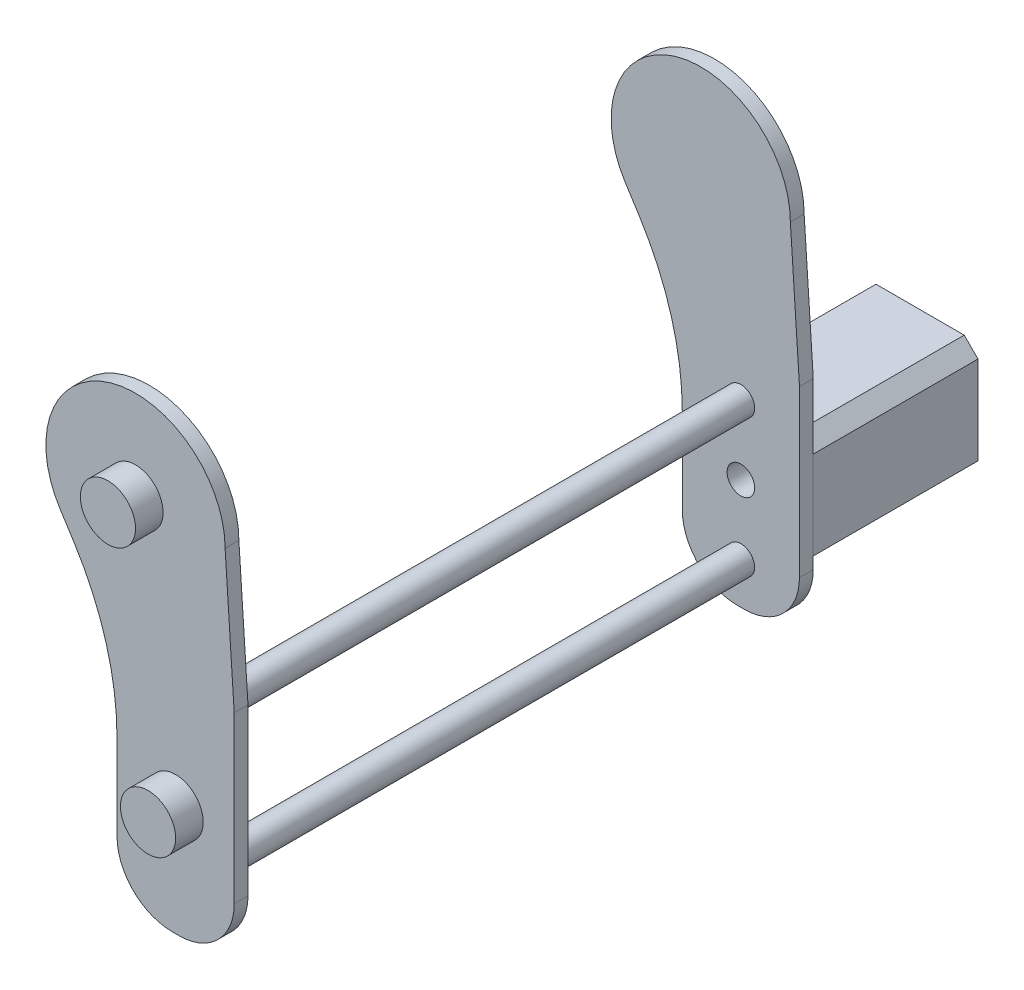
SolidWorks part; units mm, degrees
note: The reader was unsure of these and kept them because the rebuilt part matched: shared geometry of "Sketch5<3>", "Sketch5<4>".
ref_plane "Front Plane" through (0, 0, 0) normal (0, 0, 1) x (1, 0, 0)
ref_plane "Top Plane" through (0, 0, 0) normal (0, 1, 0) x (1, 0, 0)
ref_plane "Right Plane" through (0, 0, 0) normal (1, 0, 0) x (0, 0, -1)
sketch "Sketch5" plane through (0, 0, 0) normal (0, 0, 1) x (1, 0, 0)
  line L0 (14.55, -65) -> (14.55, -115) construction
  line L5 (0, 0) -> (0, -283.4803) construction
  line L7 (35.8, -50) -> (32.5, 0)
  line L11 (35.8, -68.75) -> (-6.7, -68.75)
  line L12 (35.8, -68.75) -> (35.8, -111.25)
  line L13 (35.8, -111.25) -> (-6.7, -111.25)
  line L14 (-6.7, -68.75) -> (-6.7, -111.25)
  line L15 (35.8, -68.75) -> (-6.7, -111.25) construction
  line L16 (35.8, -111.25) -> (-6.7, -68.75) construction
  line L17 (-6.7, -130) -> (35.8, -130)
  line L18 (-6.7, -130) -> (-6.7, -79.1253)
  line L19 (-6.7, -50) -> (35.8, -50) construction
  line L20 (35.8, -130) -> (35.8, -50)
  line L21 (-6.7, -130) -> (35.8, -50) construction
  line L22 (-6.7, -50) -> (35.8, -130) construction
  line L23 (-22.339, -25.4296) -> (-27.4173, -17.4511)
  line L25 (35.55, -111) -> (-6.45, -111)
  line L26 (35.55, -111) -> (35.55, -69)
  line L27 (35.55, -69) -> (-6.45, -69)
  line L28 (-6.45, -111) -> (-6.45, -69)
  line L29 (35.55, -111) -> (-6.45, -69) construction
  line L30 (35.55, -69) -> (-6.45, -111) construction
  circle A0 centre (14.55, -65) radius 5
  circle A1 centre (14.55, -115) radius 5
  circle A2 centre (0, 0) radius 32.5
  arc A3 (-6.7, -79.1253) -> (-22.339, -25.4296) centre (-106.7, -79.1253) ccw
  point P0 (14.55, -90)
  point P17 (14.55, -90)
  point P18 (14.55, -90)
  dimension "D3" = 10
  dimension "D7" = 65
  dimension "D8" = 100
  dimension "D1" = 42.5
  dimension "D2" = 50
  dimension "D4" = 14.55
  dimension "D5" = 90
  dimension "D6" = 15
  dimension "D9" = 42
extrude "Boss-Extrude4" add sketch "Sketch5" along normal blind 5 contours A2 | A3 L18 L11 L20 L7 A2 L23 A0 | L11 L14 L13 L12 | L17 L20 L13 L18 A1 | A0 | A1 | A1 L25 L28 L27 A0 L11 L14 L13 | A1 L25 L26 L27 A0 L28
extrude "Boss-Extrude5" add sketch "Sketch5<3>" along normal blind 105 contours A0 | A1
sketch "Sketch5<3>" plane through (0, 0, 0) normal (0, 0, 1) x (1, 0, 0) same geometry as "Sketch5"
fillet "Fillet3" radius 20 2 edges at (-6.7, -130, 2.5) (35.8, -130, 2.5)
sketch "Sketch9" plane through (0, 0, 0) normal (0, 0, -1) x (-1, 0, 0)
  circle A0 centre (0, 0) radius 10
  dimension "D1" = 20
extrude "Boss-Extrude8" add sketch "Sketch9" along normal blind 10
mirror "Mirror3" about plane through (14.55, -65, 105) normal (0, 0, 1) of bodies 113 107
extrude "Boss-Extrude6" add sketch "Sketch5<4>" against normal blind 60 contours A1 L25 L26 L27 A0 L28 | L27 A0 | L25 A1 | L11 L14 L13 L12
sketch "Sketch5<4>" plane through (0, 0, 0) normal (0, 0, 1) x (1, 0, 0) same geometry as "Sketch5"
chamfer "Chamfer1" distance 5 angle 45 4 edges at (-6.45, -111, -30) (35.55, -111, -30) (35.55, -69, -30) (-6.45, -69, -30)
sketch "Sketch7" plane through (0, 0, 210) normal (0, 0, 1) x (1, 0, 0)
  circle A0 centre (14.55, -90) radius 10
  point P2 (215.0266, -104.2912)
  dimension "D1" = 20
extrude "Boss-Extrude7" add sketch "Sketch7" along normal blind 10
sketch "Sketch8" plane through (0, 0, 5) normal (0, 0, 1) x (1, 0, 0)
  circle A0 centre (14.55, -90) radius 5
  dimension "D1" = 10
extrude "Cut-Extrude2" cut sketch "Sketch8" against normal blind 10 and the other way offset from surface (210 mm away) 10
equation "\"d1\"=147.64"
